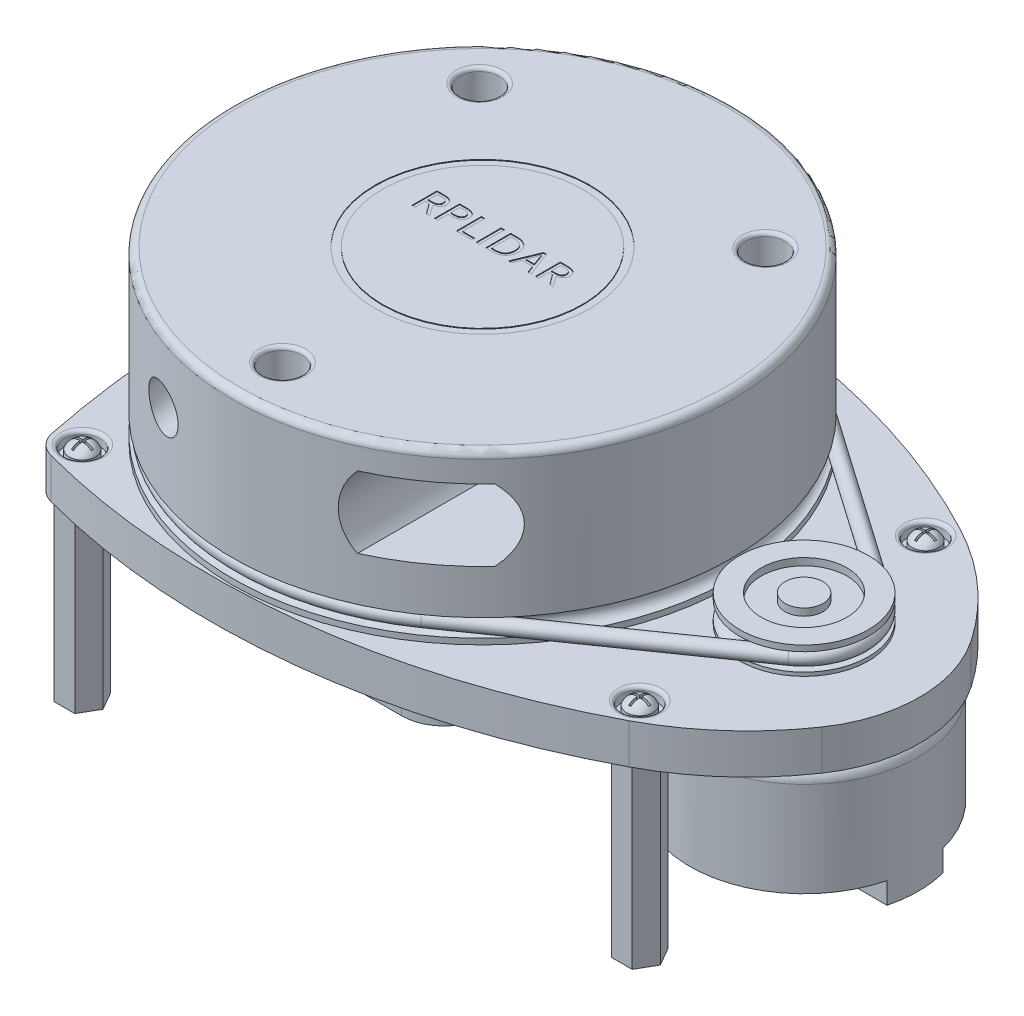
SolidWorks part; units mm, degrees
ref_plane "Front Plane" through (0, 0, 0) normal (0, 0, 1) x (1, 0, 0)
ref_plane "Top Plane" through (0, 0, 0) normal (0, 1, 0) x (1, 0, 0)
ref_plane "Right Plane" through (0, 0, 0) normal (1, 0, 0) x (0, 0, -1)
sketch "Sketch1" plane through (0, 0, 0) normal (0, 1, 0) x (1, 0, 0)
  circle A0 centre (0, 0) radius 35
  dimension "D1" = 70
extrude "puck" add sketch "Sketch1" along normal blind 23.5
fillet "Fillet1" radius 1 1 edges at (0, 23.5, 35)
sketch "Sketch2" plane through (0, 0, 0) normal (0, 0, 1) x (1, 0, 0)
  line L0 (-35, 0) -> (35, 0) construction
  line L1 (-35, 3.3) -> (-35, 0.8)
  line L2 (-35, 22.5) -> (-35, 0) construction
  line L3 (0, 0) -> (0, 35.1449) construction
  arc A0 (-35, 3.3) -> (-35, 0.8) centre (-35, 2.05) cw
  dimension "D1" = 1.25
  dimension "D2" = 0.8
revolve "groove" cut sketch "Sketch2" angle 360 about L3
sketch "Sketch3" plane through (0, 0, 0) normal (0, 0, 1) x (1, 0, 0)
  line L0 (14.4098, 19.5) -> (25.5902, 19.5)
  line L1 (25.5902, 9.5) -> (14.4098, 9.5)
  line L2 (14.4098, 19.5) -> (14.4098, 9.5) construction
  line L3 (25.5902, 19.5) -> (25.5902, 9.5) construction
  line L4 (34, 23.5) -> (-34, 23.5) construction
  arc A0 (14.4098, 19.5) -> (14.4098, 9.5) centre (20, 14.5) ccw
  arc A1 (25.5902, 9.5) -> (25.5902, 19.5) centre (20, 14.5) ccw
  dimension "D1" = 15
  dimension "D2" = 10
  dimension "D3" = 4
  dimension "D4" = 20
extrude "cut_sensor_tunnel" cut sketch "Sketch3" along normal through all
ref_axis "main_axis" through (0, 55.9429, 0) along (0, -1, 0)
ref_plane "Plane3" through (0, 0, 0) normal (0.1736, 0, 0.9848) x (0, -1, 0)
sketch "Sketch4" plane through (0, 0, 0) normal (0, 1, 0) x (1, 0, 0)
  line L0 (-28, 28) -> (42, 20) construction
  line L1 (42, 20) -> (42, -20) construction
  line L2 (42, -20) -> (-28, -28) construction
  line L3 (-28, -28) -> (-28, 28) construction
  circle A0 centre (0, 0) radius 35 construction
  circle A1 centre (-28, 28) radius 3.6 construction
  circle A2 centre (-28, -28) radius 3.6 construction
  arc A5 (-28.9266, 31.4787) -> (43.6876, 23.18) centre (-3.1888, -65.1524) cw
  arc A6 (-31.5287, 28.7129) -> (-31.5287, -28.7129) centre (110.6, 0) ccw
  circle A7 centre (42, 20) radius 3.6 construction
  circle A8 centre (42, -20) radius 3.6 construction
  arc A9 (-28.9266, 31.4787) -> (-31.5287, 28.7129) centre (-28, 28) ccw
  arc A10 (43.6876, -23.18) -> (-28.9266, -31.4787) centre (-3.1888, 65.1524) cw
  arc A11 (57.9337, -10.4572) -> (57.9337, 10.4572) centre (42.6727, 0) ccw
  arc A12 (43.6876, 23.18) -> (57.9337, 10.4572) centre (24.937, -12.153) cw
  arc A13 (57.9337, -10.4572) -> (43.6876, -23.18) centre (24.937, 12.153) cw
  arc A14 (-31.5287, -28.7129) -> (-28.9266, -31.4787) centre (-28, -28) ccw
  point P2 (-28, 0)
  point P21 (-35, 0)
  point P34 (61.1727, 0)
  dimension "D4" = 7.2
  dimension "D6" = 37
  dimension "D7" = 100
  dimension "D9" = 145
  dimension "D10" = 42
  dimension "D3" = 40
  dimension "D1" = 56
  dimension "D2" = 40
  dimension "D5" = 70
  dimension "D11" = 28
extrude "boss_board" add sketch "Sketch4" against normal blind 5.6 from offset 0.5 contours A6 A14 A10 A13 A11 A12 A5 A9 offset against normal yes
sketch "Sketch5" plane through (0, -6.1, 0) normal (0, -1, 0) x (1, 0, 0)
  line L1 (-26.5566, 30.5) -> (-29.4434, 30.5)
  line L2 (-29.4434, 30.5) -> (-30.8868, 28)
  line L3 (-30.8868, 28) -> (-29.4434, 25.5)
  line L4 (-29.4434, 25.5) -> (-26.5566, 25.5)
  line L5 (-26.5566, 25.5) -> (-25.1132, 28)
  line L6 (-25.1132, 28) -> (-26.5566, 30.5)
  line L7 (-26.5566, -25.5) -> (-29.4434, -25.5)
  line L8 (-29.4434, -25.5) -> (-30.8868, -28)
  line L9 (-30.8868, -28) -> (-29.4434, -30.5)
  line L10 (-29.4434, -30.5) -> (-26.5566, -30.5)
  line L11 (-26.5566, -30.5) -> (-25.1132, -28)
  line L12 (-25.1132, -28) -> (-26.5566, -25.5)
  line L13 (43.4434, 22.5) -> (40.5566, 22.5)
  line L14 (40.5566, 22.5) -> (39.1132, 20)
  line L15 (39.1132, 20) -> (40.5566, 17.5)
  line L16 (40.5566, 17.5) -> (43.4434, 17.5)
  line L17 (43.4434, 17.5) -> (44.8868, 20)
  line L18 (44.8868, 20) -> (43.4434, 22.5)
  line L19 (43.4434, -17.5) -> (40.5566, -17.5)
  line L20 (40.5566, -17.5) -> (39.1132, -20)
  line L21 (39.1132, -20) -> (40.5566, -22.5)
  line L22 (40.5566, -22.5) -> (43.4434, -22.5)
  line L23 (43.4434, -22.5) -> (44.8868, -20)
  line L24 (44.8868, -20) -> (43.4434, -17.5)
  circle A0 centre (-28, 28) radius 2.5 construction
  circle A1 centre (-28, -28) radius 2.5 construction
  circle A2 centre (42, 20) radius 2.5 construction
  circle A3 centre (42, -20) radius 2.5 construction
  dimension "D1" = 5
  dimension "D2" = 70.4557
  dimension "D3" = 56
  dimension "D4" = 40
extrude "hex_standoffs" add sketch "Sketch5" along normal blind 25
sketch "Sketch23" plane through (0, -0.5, 0) normal (0, 1, 0) x (1, 0, 0)
  line L0 (-26.5566, 30.5) -> (-29.4434, 25.5) construction
  circle A0 centre (-28, 28) radius 2.5
  circle A1 centre (42, 20) radius 2.5
  circle A2 centre (42, -20) radius 2.5
  circle A3 centre (-28, -28) radius 2.5
  dimension "D1" = 5
extrude "screw_seats" cut sketch "Sketch23" against normal blind 1.5
fillet "fillet_screw_seats" radius 0.5 4 edges at (-28, -0.5, 30.5) (42, -0.5, 22.5) (42, -0.5, -17.5) (-28, -0.5, -25.5)
ref_axis "Axis2" through (42, -2, -20) along (0, 1, 0)
ref_axis "Axis3" through (42, -2, 20) along (0, 1, 0)
ref_axis "Axis4" through (-28, -2, 28) along (0, 1, 0)
ref_axis "Axis5" through (-28, -2, -28) along (0, 1, 0)
ref_plane "Plane2" through (-28, 0, 0) normal (1, 0, 0) x (0, 1, 0)
sketch "Sketch24" plane through (-28, 0, 0) normal (1, 0, 0) x (0, 1, 0)
  line L0 (-2, -28) -> (10.5165, -28) construction
  line L1 (-2, -30.5) -> (-2, -25.5) construction
  line L2 (-2, -28) -> (-2, -26.15)
  line L3 (-2, -26.15) -> (-1.0411, -26.15)
  line L4 (-2, -28) -> (-1, -28)
  line L5 (-1, -28) -> (-1, -27.75)
  line L6 (-1, -27.75) -> (0, -27.75)
  line L7 (0, -27.75) -> (0, -28.9522) construction
  line L8 (0, -31.4787) -> (0, -28.7129) construction
  arc A0 (-1.0411, -26.15) -> (0, -27.75) centre (-1.75, -27.75) cw
  dimension "D4" = 1.75
  dimension "D1" = 3.7
  dimension "D2" = 2
  dimension "D3" = 0.5
  dimension "D5" = 1
revolve "revolve_screw_head" add sketch "Sketch24" angle 360 about L0
sketch "Sketch25" plane through (0, -0.5, 0) normal (0, 1, 0) x (1, 0, 0)
  line L0 (-27.85, 28.15) -> (-26.6, 28.15)
  line L1 (-28.15, 26.6) -> (-27.85, 26.6)
  line L2 (-28.15, 26.6) -> (-28.15, 27.85)
  line L3 (-28.15, 29.4) -> (-27.85, 29.4)
  line L4 (-27.85, 26.6) -> (-27.85, 27.85)
  line L5 (-28.15, 26.6) -> (-27.85, 29.4) construction
  line L6 (-28.15, 29.4) -> (-27.85, 26.6) construction
  line L7 (-29.4, 27.85) -> (-28.15, 27.85)
  line L8 (-29.4, 27.85) -> (-29.4, 28.15)
  line L9 (-29.4, 28.15) -> (-28.15, 28.15)
  line L10 (-26.6, 27.85) -> (-26.6, 28.15)
  line L11 (-29.4, 27.85) -> (-26.6, 28.15) construction
  line L12 (-29.4, 28.15) -> (-26.6, 27.85) construction
  line L13 (-27.85, 28.15) -> (-27.85, 29.4)
  line L14 (-28.15, 28.15) -> (-28.15, 29.4)
  line L16 (-27.85, 27.85) -> (-26.6, 27.85)
  point P0 (-28, 28)
  point P6 (-28, 28)
  dimension "D1" = 0.3
  dimension "D2" = 1.4
  dimension "D3" = 1.4
extrude "Cut-Extrude5" cut sketch "Sketch25" against normal blind 0.5 and the other way blind 1.5 contours L14 L3 L13 L0 L10 L16 L4 L1 L2 L7 L8 L9
sketch "Sketch26" plane through (0, -0.5, 0) normal (0, 1, 0) x (1, 0, 0)
  point P0 (42, 20)
  point P1 (42, -20)
  point P3 (-28, -28)
  point P5 (-28, 28)
pattern_sketch "Sketch-Pattern1" of "revolve_screw_head", "Cut-Extrude5" driven by "Sketch26"
sketch "Sketch6" plane through (0, -6.1, 0) normal (0, -1, 0) x (1, 0, 0)
  line L0 (42, 20) -> (42, -20) construction
  circle A0 centre (45, 0) radius 16
  dimension "D1" = 32
  dimension "D2" = 3
extrude "motor_body" add sketch "Sketch6" along normal blind 15 separate body
ref_axis "Axis1" through (45, -21.1, 0) along (0, 1, 0)
sketch "Sketch8" plane through (0, 0, 0) normal (0, 0, 1) x (1, 0, 0)
  line L0 (45, 4.1) -> (47.65, 4.1)
  line L1 (47.65, 4.1) -> (47.65, 3.1)
  line L2 (47.65, 3.1) -> (51, 3.1)
  line L3 (51, 3.1) -> (51, 4.1)
  line L4 (51, 4.1) -> (54, 4.1)
  line L5 (54, 4.1) -> (54, 3.2839)
  line L6 (54, 0.8161) -> (54, 0.3)
  line L7 (54, 0.3) -> (47, 0.3)
  line L8 (47, 0.3) -> (47, 0)
  line L9 (57.9337, 0) -> (43.6876, 0) construction
  line L10 (45, -21.1) -> (45, -6.1) construction
  line L11 (45, 4.1) -> (45, 0)
  line L12 (45, 0) -> (45, 20.7967) construction
  line L13 (61.1727, -0.5) -> (57.9337, -0.5) construction
  line L14 (47, 0) -> (45, 0)
  arc A0 (54, 3.2839) -> (54, 0.8161) centre (53.8, 2.05) ccw
  arc A1 (35, 3.3) -> (35, 0.8) centre (35, 2.05) ccw construction
  point P7 (33.75, 2.05)
  dimension "D7" = 1.25
  dimension "D1" = 12
  dimension "D2" = 5.3
  dimension "D3" = 4.6
  dimension "D4" = 18
  dimension "D5" = 4
  dimension "D6" = 0.8
  dimension "D8" = 1
  dimension "D9" = 8.8
revolve "motor_pulley" add sketch "Sketch8" angle 360 about L12
sketch "Sketch9" plane through (0, -6.1, 0) normal (0, -1, 0) x (1, 0, 0)
  circle A0 centre (0, 0) radius 30
  dimension "D1" = 60
extrude "mould_bottom_disc" add sketch "Sketch9" along normal blind 3.3
sketch "Sketch10" plane through (0, -9.4, 0) normal (0, -1, 0) x (1, 0, 0)
  line L1 (-22.8273, 28.5) -> (23.1727, 28.5)
  line L2 (-22.8273, 28.5) -> (-22.8273, -28.5)
  line L3 (-22.8273, -28.5) -> (23.1727, -28.5)
  line L4 (23.1727, 28.5) -> (23.1727, -28.5)
  arc A0 (57.9337, -10.4572) -> (57.9337, 10.4572) centre (42.6727, 0) ccw construction
  point P4 (24.1727, 0)
  point P5 (23.1727, 0)
  dimension "D1" = 57
  dimension "D2" = 46
  dimension "D3" = 1
extrude "boss_circuit" add sketch "Sketch10" along normal blind 1.1
fillet "fillet_circuit_board" radius 6 4 edges at (-22.8273, -9.95, 28.5) (23.1727, -9.95, -28.5) (23.1727, -9.95, 28.5) (-22.8273, -9.95, -28.5)
sketch "Sketch11" plane through (0, 0, 0) normal (0, 0, 1) x (1, 0, 0)
  arc A0 (-35, 0.8) -> (-35, 3.3) centre (-35, 2.05) ccw construction
  arc A1 (35, 3.3) -> (35, 0.8) centre (35, 2.05) ccw construction
  arc A2 (36.2, 0.8) -> (36.2, 3.3) centre (36.2, 2.05) ccw construction
  point P0 (-33.75, 2.05)
  point P1 (33.75, 2.05)
  point P5 (37.45, 2.05)
ref_plane "belt_plane" through (0, 2.05, 0) normal (0, 1, 0) x (1, 0, 0)
sketch "Sketch12" plane through (0, 2.05, 0) normal (0, 1, 0) x (1, 0, 0)
  line L0 (19.3125, 27.6783) -> (49.5778, 6.5608)
  line L1 (49.5778, -6.5608) -> (19.3125, -27.6783)
  arc A0 (19.3125, 27.6783) -> (19.3125, -27.6783) centre (0, 0) ccw
  arc A1 (49.5778, -6.5608) -> (49.5778, 6.5608) centre (45, 0) ccw
  circle A2 centre (45, 0) radius 8 construction
  dimension "D1" = 16
sweep "sweep_band" add path "Sketch12" circular profile diameter 2 parameters "D3"=2
fillet "Fillet3" radius 1.75 1 edges at (45, -6.1, -16)
sketch "Sketch18" plane through (0, 23.5, 0) normal (0, 1, 0) x (1, 0, 0)
  line L0 (-20, 19.5959) -> (20, 19.5959) construction
  line L1 (20, 19.5959) -> (0, -28) construction
  line L2 (0, -28) -> (-20, 19.5959) construction
  line L3 (-20, 19.5959) -> (0, 0) construction
  line L4 (0, 0) -> (0, -28) construction
  circle A0 centre (-20, 19.5959) radius 2.75
  circle A1 centre (20, 19.5959) radius 2.75
  circle A2 centre (0, -28) radius 2.75
  point P6 (0, 19.5959)
  dimension "D1" = 5.5
  dimension "D2" = 28
  dimension "D3" = 28
  dimension "D4" = 40
extrude "top_puck_holes" cut sketch "Sketch18" against normal blind 8
fillet "fillet_puck_holes" radius 0.5 3 edges at (0, 23.5, 30.75) (20, 23.5, -16.8459) (-20, 23.5, -16.8459)
sketch "Sketch19" plane through (0, 23.5, 0) normal (0, 1, 0) x (1, 0, 0)
  circle A0 centre (0, 0) radius 13.98
  circle A1 centre (0, 0) radius 15
  dimension "D1" = 1.02
  dimension "D2" = 30
extrude "top_ring_aesthetic" cut sketch "Sketch19" against normal blind 0.1
sketch "Sketch28" plane through (0, 23.5, 0) normal (0, 1, 0) x (1, 0, 0)
  text T0 "RPLIDAR" font "Corbel" height 3.5
extrude "RPLIDAR_text" cut sketch "Sketch28" against normal blind 0.1
sketch "Sketch30" plane through (0, -21.1, 0) normal (0, -1, 0) x (1, 0, 0)
  line L0 (29.4826, 3.9) -> (60.5174, 3.9)
  line L1 (60.5174, -3.9) -> (29.4826, -3.9)
  line L2 (60.5174, 3.9) -> (60.5174, -3.9) construction
  arc A0 (29.4826, 3.9) -> (29.4826, -3.9) centre (45, 0) ccw
  arc A1 (60.5174, -3.9) -> (60.5174, 3.9) centre (45, 0) ccw
  circle A2 centre (45, 0) radius 16 construction
  dimension "D1" = 7.8
extrude "motor_plastic_feature" add sketch "Sketch30" along normal blind 3
sketch "Sketch31" plane through (0, 0, 0) normal (0.1736, 0, 0.9848) x (0, -1, 0)
  line L0 (-14.5, 19.6098) -> (-14.5, -17.3902) construction
  circle A0 centre (-14.5, -17.3902) radius 3.5
  dimension "D2" = 7
  dimension "D1" = 37
extrude "cut_optics" cut sketch "Sketch31" along normal through all draft 1
sketch "Sketch37" plane through (0, -31.1, 0) normal (0, -1, 0) x (1, 0, 0)
  line L0 (39.1132, -20) -> (44.8868, -20) construction
  line L1 (-30.8868, -28) -> (-25.1132, -28) construction
  line L2 (39.1132, 20) -> (44.8868, 20) construction
  line L3 (44.8868, 20) -> (43.4434, 22.5) construction
  line L4 (-30.8868, 28) -> (-25.1132, 28) construction
  line L5 (-26.5566, 25.5) -> (-25.1132, 28) construction
  circle A0 centre (-28, 28) radius 1.25
  circle A1 centre (42, 20) radius 1.25
  circle A2 centre (-28, -28) radius 1.25
  circle A3 centre (42, -20) radius 1.25
  dimension "D1" = 2.5
extrude "drill_standoffs" cut sketch "Sketch37" against normal blind 10
sketch "Sketch38" plane through (0, -31.1, 0) normal (0, -1, 0) x (1, 0, 0)
  line L1 (-28, 28) -> (42, 20)
  line L2 (-28, 28) -> (-28, -28)
  line L3 (-28, -28) -> (42, -20)
  line L4 (42, 20) -> (42, -20)
  dimension "D1" = 56
  dimension "D2" = 40
  dimension "D3" = 70
  dimension "D4" = 28
ref_plane "Plane4" through (0, 14.5, 0) normal (0, 1, 0) x (1, 0, 0)
